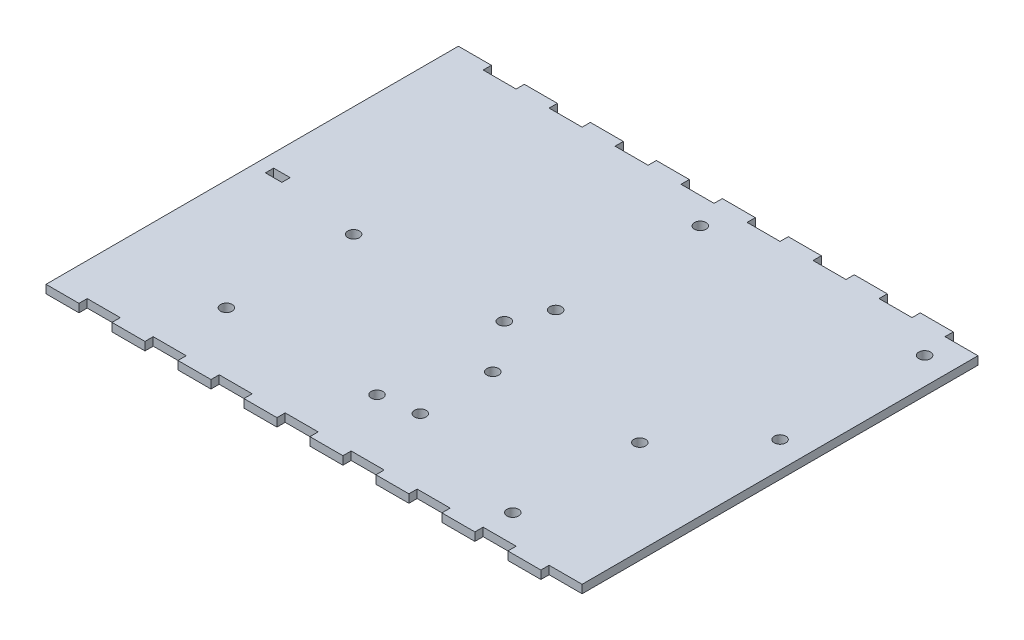
SolidWorks part; units mm, degrees
ref_plane "Front" through (0, 0, 0) normal (0, 0, 1) x (1, 0, 0)
ref_plane "Top" through (0, 0, 0) normal (0, 1, 0) x (1, 0, 0)
ref_plane "Right" through (0, 0, 0) normal (1, 0, 0) x (0, 0, -1)
sketch "Sketch1" plane through (0, 0, 0) normal (0, 1, 0) x (1, 0, 0)
  line L1 (0, 0) -> (203.2, 0)
  line L2 (0, 0) -> (0, 152.4)
  line L3 (0, 152.4) -> (203.2, 152.4)
  line L4 (203.2, 0) -> (203.2, 152.4)
  dimension "D1" = 203.2
  dimension "D2" = 152.4
extrude "Boss-Extrude1" add sketch "Sketch1" along normal blind 3.175
sketch "Sketch2" plane through (0, 3.175, 0) normal (0, 1, 0) x (1, 0, 0)
  line L0 (25.4, 0) -> (25.4, -3.175)
  line L1 (0, 0) -> (12.7, 0)
  line L2 (0, 0) -> (0, -3.175)
  line L3 (0, -3.175) -> (12.7, -3.175)
  line L4 (12.7, 0) -> (12.7, -3.175)
  line L5 (25.4, 0) -> (38.1, 0)
  line L6 (38.1, 0) -> (38.1, -3.175)
  line L7 (25.4, -3.175) -> (38.1, -3.175)
  line L8 (50.8, 0) -> (50.8, -3.175)
  line L9 (50.8, 0) -> (63.5, 0)
  line L10 (63.5, 0) -> (63.5, -3.175)
  line L11 (50.8, -3.175) -> (63.5, -3.175)
  line L12 (76.2, 0) -> (76.2, -3.175)
  line L13 (76.2, 0) -> (88.9, 0)
  line L14 (88.9, 0) -> (88.9, -3.175)
  line L15 (76.2, -3.175) -> (88.9, -3.175)
  line L16 (101.6, 0) -> (101.6, -3.175)
  line L17 (101.6, 0) -> (114.3, 0)
  line L18 (114.3, 0) -> (114.3, -3.175)
  line L19 (101.6, -3.175) -> (114.3, -3.175)
  line L20 (127, 0) -> (127, -3.175)
  line L21 (127, 0) -> (139.7, 0)
  line L22 (139.7, 0) -> (139.7, -3.175)
  line L23 (127, -3.175) -> (139.7, -3.175)
  line L24 (152.4, 0) -> (152.4, -3.175)
  line L25 (152.4, 0) -> (165.1, 0)
  line L26 (165.1, 0) -> (165.1, -3.175)
  line L27 (152.4, -3.175) -> (165.1, -3.175)
  line L28 (177.8, 0) -> (177.8, -3.175)
  line L29 (177.8, 0) -> (190.5, 0)
  line L30 (190.5, 0) -> (190.5, -3.175)
  line L31 (177.8, -3.175) -> (190.5, -3.175)
  line L32 (0, 76.2) -> (203.2, 76.2) construction
  line L33 (0, 152.4) -> (0, 0) construction
  line L34 (203.2, 0) -> (203.2, 152.4) construction
  line L35 (177.8, 152.4) -> (190.5, 152.4)
  line L36 (190.5, 152.4) -> (190.5, 155.575)
  line L37 (177.8, 155.575) -> (190.5, 155.575)
  line L38 (177.8, 152.4) -> (177.8, 155.575)
  line L39 (152.4, 152.4) -> (165.1, 152.4)
  line L40 (165.1, 152.4) -> (165.1, 155.575)
  line L41 (152.4, 155.575) -> (165.1, 155.575)
  line L42 (152.4, 152.4) -> (152.4, 155.575)
  line L43 (127, 152.4) -> (139.7, 152.4)
  line L44 (139.7, 152.4) -> (139.7, 155.575)
  line L45 (127, 155.575) -> (139.7, 155.575)
  line L46 (127, 152.4) -> (127, 155.575)
  line L47 (101.6, 152.4) -> (114.3, 152.4)
  line L48 (114.3, 152.4) -> (114.3, 155.575)
  line L49 (101.6, 155.575) -> (114.3, 155.575)
  line L50 (101.6, 152.4) -> (101.6, 155.575)
  line L51 (76.2, 152.4) -> (88.9, 152.4)
  line L52 (88.9, 152.4) -> (88.9, 155.575)
  line L53 (76.2, 155.575) -> (88.9, 155.575)
  line L54 (76.2, 152.4) -> (76.2, 155.575)
  line L55 (50.8, 152.4) -> (63.5, 152.4)
  line L56 (63.5, 152.4) -> (63.5, 155.575)
  line L57 (50.8, 155.575) -> (63.5, 155.575)
  line L58 (50.8, 152.4) -> (50.8, 155.575)
  line L59 (25.4, 152.4) -> (38.1, 152.4)
  line L60 (38.1, 152.4) -> (38.1, 155.575)
  line L61 (25.4, 155.575) -> (38.1, 155.575)
  line L62 (25.4, 152.4) -> (25.4, 155.575)
  line L63 (0, 155.575) -> (12.7, 155.575)
  line L64 (12.7, 152.4) -> (12.7, 155.575)
  line L65 (0, 152.4) -> (12.7, 152.4)
  line L66 (0, 152.4) -> (0, 155.575)
  dimension "D1" = 3.175
  dimension "D2" = 12.7
  dimension "D3" = 8
extrude "Boss-Extrude2" add sketch "Sketch2" against normal blind 3.175 separate body
sketch "Sketch4" plane through (163.3185, 3.175, 18.1289) normal (0, 1, 0) x (-1, 0, 0)
  line L0 (91.7685, -38.3289) -> (91.7685, -94.3289) construction
  line L1 (62.2685, -94.3289) -> (141.2685, -94.3289) construction
  line L2 (59.2685, -91.3289) -> (59.2685, -41.3289) construction
  line L3 (62.2685, -38.3289) -> (141.2685, -38.3289) construction
  line L4 (144.2685, -91.3289) -> (144.2685, -41.3289) construction
  line L5 (-39.8815, -170.5289) -> (163.3185, -170.5289) construction
  line L6 (163.3185, -170.5289) -> (163.3185, -18.1289) construction
  arc A0 (62.2685, -94.3289) -> (59.2685, -91.3289) centre (62.2685, -91.3289) cw construction
  arc A1 (141.2685, -94.3289) -> (144.2685, -91.3289) centre (141.2685, -91.3289) ccw construction
  arc A2 (141.2685, -38.3289) -> (144.2685, -41.3289) centre (141.2685, -41.3289) cw construction
  arc A3 (59.2685, -41.3289) -> (62.2685, -38.3289) centre (62.2685, -41.3289) cw construction
  circle A4 centre (62.7685, -41.8289) radius 2.25
  circle A5 centre (62.7685, -90.8289) radius 2.25
  circle A6 centre (120.7685, -90.8289) radius 2.25
  circle A7 centre (120.7685, -41.8289) radius 2.25
  point P7 (59.2685, -94.3289)
  point P12 (144.2685, -38.3289)
  point P15 (59.2685, -38.3289)
  dimension "D3" = 3
  dimension "D4" = 4.5
  dimension "D1" = 56
  dimension "D2" = 85
  dimension "D5" = 49
  dimension "D6" = 3.5
  dimension "D7" = 3.5
  dimension "D8" = 58
  dimension "D9" = 76.2
  dimension "D10" = 19.05
extrude "Cut-Extrude1" cut sketch "Sketch4" against normal through all
sketch "Sketch5" plane through (307.482, 3.175, -268.649) normal (0, 1, 0) x (-1, 0, 0)
  line L0 (126.4071, 207.5541) -> (126.4071, 260.8541) construction
  line L1 (126.4071, 260.8541) -> (190.176, 260.8541) construction
  line L2 (190.176, 260.8541) -> (192.3071, 258.7229) construction
  line L3 (195.2071, 245.0129) -> (195.2071, 213.2041) construction
  line L4 (195.2071, 213.2041) -> (192.3071, 210.3041) construction
  line L5 (192.3071, 210.3041) -> (192.3071, 207.5541) construction
  line L6 (192.3071, 207.5541) -> (126.4071, 207.5541) construction
  line L7 (192.3071, 258.7229) -> (192.3071, 247.9129) construction
  line L8 (192.3071, 247.9129) -> (195.2071, 245.0129) construction
  circle A0 centre (140.4071, 210.3041) radius 2.25
  circle A1 centre (141.5071, 258.1041) radius 2.25
  circle A2 centre (192.3071, 215.0041) radius 2.25
  circle A3 centre (192.3071, 242.9041) radius 2.25
  dimension "ArduinoHoles" = 4.5
  dimension "D1" = 53.3
  dimension "D2" = 68.8
  dimension "D5" = 14
  dimension "D9" = 1.1
  dimension "D10" = 4.7
  dimension "D4" = 15.2
  dimension "D6" = 2.75
  dimension "D12" = 50.8
  dimension "D13" = 45
  dimension "D14" = 45
  dimension "D16" = 45
  dimension "D7" = 51.9
  dimension "D8" = 51.9
  dimension "D11" = 2.75
  dimension "D15" = 10.81
  dimension "D17" = 31.8089
extrude "Cut-Extrude2" cut sketch "Sketch5" against normal through all
sketch "Sketch10" plane through (154.7382, 3.175, -89.7842) normal (0, 1, 0) x (0, 0, -1)
  line L0 (-4.9142, -42.1118) -> (53.9458, -42.1118) construction
  line L1 (-7.2342, -39.7918) -> (-7.2342, 49.5682) construction
  line L2 (-4.9142, 51.8882) -> (53.9458, 51.8882) construction
  line L3 (56.2658, -39.7918) -> (56.2658, 49.5682) construction
  line L4 (-7.2342, -42.1118) -> (56.2658, 51.8882) construction
  line L5 (-7.2342, 51.8882) -> (56.2658, -42.1118) construction
  line L7 (62.6158, -48.4618) -> (62.6158, 154.7382) construction
  line L8 (-3.4238, 48.0682) -> (-3.4238, -38.2918) construction
  line L9 (-89.7842, -48.4618) -> (62.6158, -48.4618) construction
  arc A0 (-4.9142, -42.1118) -> (-7.2342, -39.7918) centre (-4.9142, -39.7918) cw construction
  arc A1 (53.9458, -42.1118) -> (56.2658, -39.7918) centre (53.9458, -39.7918) ccw construction
  arc A2 (53.9458, 51.8882) -> (56.2658, 49.5682) centre (53.9458, 49.5682) cw construction
  arc A3 (-4.9142, 51.8882) -> (-7.2342, 49.5682) centre (-4.9142, 49.5682) ccw construction
  circle A4 centre (-17.0842, 112.1882) radius 2.25 construction
  circle A5 centre (-3.4238, 48.0682) radius 2.25
  circle A6 centre (52.4558, 48.2859) radius 2.25
  circle A7 centre (-3.4238, -38.2918) radius 2.25
  circle A8 centre (52.4558, -38.0741) radius 2.25
  point P0 (24.5158, 4.8882)
  dimension "D3" = 2.32
  dimension "D6" = 4.5
  dimension "D7" = 4.5
  dimension "D1" = 63.5
  dimension "D2" = 94
  dimension "D5" = 6.35
  dimension "D8" = 55.88
  dimension "D10" = 43.18
  dimension "D12" = 86.36
  dimension "D4" = 6.35
  dimension "D11" = 2
extrude "Cut-Extrude3" cut sketch "Sketch10" against normal through all both and the other way through all
combine bodies "Combine1" operation type add bodies to combine 102 104 106 108 110 112 114 116 117 122 103 105 107 109 111 113 115
sketch "Sketch11" plane through (0, 3.175, 0) normal (0, 1, 0) x (1, 0, 0)
  line L0 (0, 76.2) -> (203.2, 76.2) construction
  line L1 (0, 155.575) -> (0, -3.175) construction
  line L2 (203.2, 0) -> (203.2, 152.4) construction
  line L4 (5.08, 76.2) -> (11.43, 76.2)
  line L5 (5.08, 76.2) -> (5.08, 79.375)
  line L6 (5.08, 79.375) -> (11.43, 79.375)
  line L7 (11.43, 76.2) -> (11.43, 79.375)
  dimension "D1" = 3.175
  dimension "D2" = 6.35
  dimension "D3" = 5.08
extrude "Cut-Extrude4" cut sketch "Sketch11" against normal through all
equation "\"I1\" = 4.5mm"
equation "\"D4@Sketch4\"= \"I1\""
equation "\"ArduinoHoles@Sketch5\"= \"I1\""
equation "\"D6@Sketch10\"= \"I1\""
equation "\"D7@Sketch10\"= \"I1\""
